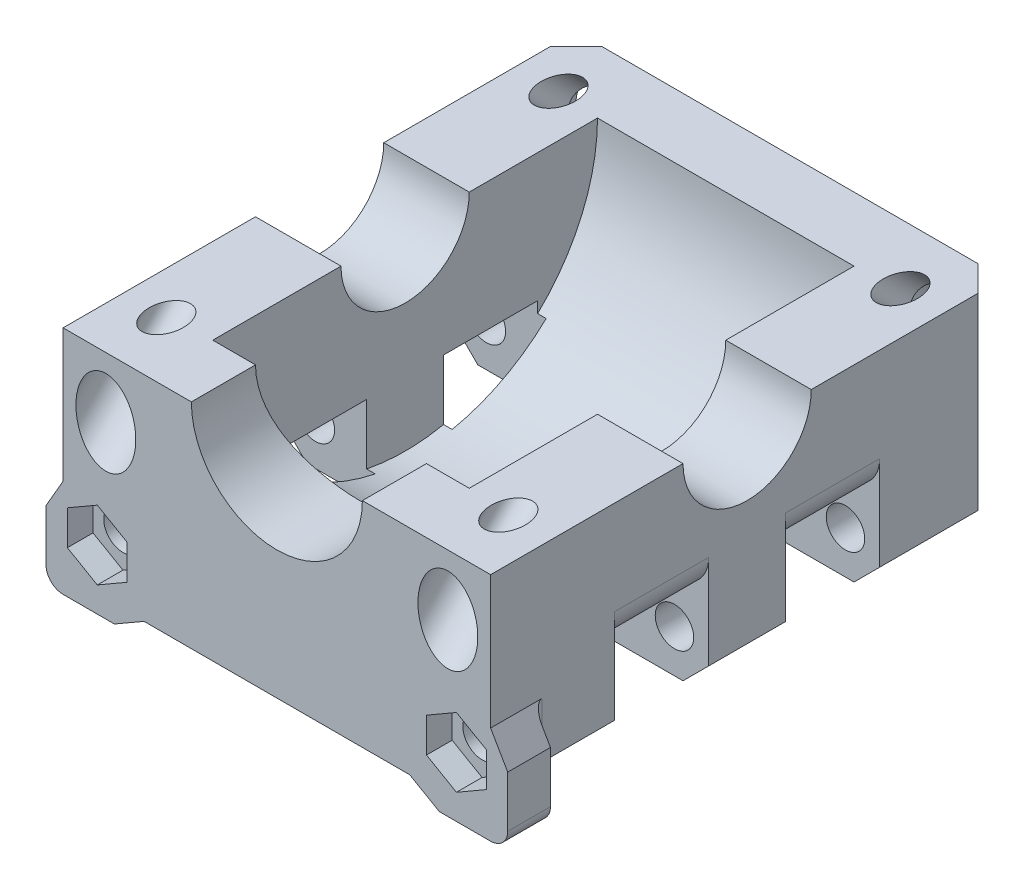
SolidWorks part; units mm, degrees
ref_plane "Front Plane" through (0, 0, 0) normal (0, 0, 1) x (1, 0, 0)
ref_plane "Top Plane" through (0, 0, 0) normal (0, 1, 0) x (1, 0, 0)
ref_plane "Right Plane" through (0, 0, 0) normal (1, 0, 0) x (0, 0, -1)
sketch "Sketch1" plane through (0, 0, 0) normal (0, 1, 0) x (1, 0, 0)
  line L1 (-25, 30) -> (25, 30)
  line L2 (-25, 30) -> (-25, -30)
  line L3 (-25, -30) -> (25, -30)
  line L4 (25, 30) -> (25, -30)
  line L5 (-25, 30) -> (25, -30) construction
  line L6 (-25, -30) -> (25, 30) construction
  point P0 (0, 0)
  dimension "D1" = 50
  dimension "D2" = 60
extrude "Boss-Extrude1" add sketch "Sketch1" along normal blind 25
sketch "Sketch2" plane through (-25, 0, 0) normal (-1, 0, 0) x (0, 0, 1)
  line L3 (-30, 25) -> (30, 25) construction
  line L6 (-30, 25) -> (-30, 0) construction
  circle A1 centre (0, 25) radius 22.5
  dimension "D1" = 45
  dimension "D2" = 7.5
extrude "Cut-Extrude1" cut sketch "Sketch2" against normal blind 30 from offset 10 offset against normal yes
sketch "Sketch3" plane through (-25, 0, 0) normal (-1, 0, 0) x (0, 0, 1)
  line L0 (-30, 25) -> (30, 25) construction
  circle A0 centre (0, 25) radius 7.5
  dimension "D1" = 15
extrude "Cut-Extrude2" cut sketch "Sketch3" against normal through all
sketch "Sketch4" plane through (0, 0, 30) normal (0, 0, 1) x (1, 0, 0)
  line L0 (-25, 25) -> (25, 25) construction
  circle A0 centre (0, 25) radius 10
  dimension "D1" = 20
extrude "Cut-Extrude3" cut sketch "Sketch4" against normal blind 10
sketch "Sketch10" plane through (25, 0, 0) normal (1, 0, 0) x (0, 0, -1)
  line L0 (-30, 0) -> (30, 0) construction
  line L1 (-4.5, 0) -> (-15.5, 0)
  line L2 (-4.5, 0) -> (-4.5, 10)
  line L3 (-4.5, 10) -> (-15.5, 10)
  line L4 (-15.5, 0) -> (-15.5, 10)
  line L5 (-30, 25) -> (-30, 0) construction
  line L6 (4.5, 0) -> (15.5, 0)
  line L7 (4.5, 0) -> (4.5, 10)
  line L8 (4.5, 10) -> (15.5, 10)
  line L9 (15.5, 0) -> (15.5, 10)
  arc A1 (-7.5, 25) -> (7.5, 25) centre (0, 25) ccw construction
  dimension "D1" = 10
  dimension "D2" = 10
  dimension "D3" = 9
  dimension "D4" = 11
  dimension "D5" = 11
  dimension "D6" = 14.5
  dimension "D7" = 4.5
  dimension "D8" = 4.5
extrude "Cut-Extrude9" cut sketch "Sketch10" against normal blind 11
sketch "Sketch11" plane through (0, 0, -4.5) normal (0, 0, -1) x (-1, 0, 0)
  line L0 (-25, 10) -> (-25, 0) construction
  line L1 (-14, 0) -> (-25, 0) construction
  circle A0 centre (-21, 5) radius 2.25
  dimension "D3" = 4.5
  dimension "D1" = 4
  dimension "D2" = 5
extrude "Cut-Extrude10" cut sketch "Sketch11" against normal through all both and the other way through all
mirror "Mirror1" about plane through (0, 0, 0) normal (1, 0, 0) of "Cut-Extrude9", "Cut-Extrude10"
ref_plane "Plane1" through (0, -2.5, 2.5) normal (0, -0.7071, 0.7071) x (1, 0, 0)
sketch "Sketch12" plane through (0, -2.5, 2.5) normal (0, -0.7071, 0.7071) x (1, 0, 0)
  line L0 (-25, 38.8909) -> (-25, 21.2132) construction
  line L2 (-25, 38.8909) -> (-10, 38.8909) construction
  line L3 (10, 38.8909) -> (25, 38.8909) construction
  circle A0 centre (20, 33.8909) radius 2
  circle A1 centre (-20, 33.8909) radius 2
  dimension "D1" = 4
  dimension "D2" = 4
  dimension "D3" = 40
  dimension "D4" = 5
  dimension "D5" = 5
  dimension "D6" = 5
extrude "Cut-Extrude11" cut sketch "Sketch12" against normal through all both and the other way through all
sketch "Sketch13" plane through (0, -2.5, 2.5) normal (0, -0.7071, 0.7071) x (1, 0, 0)
  circle A0 centre (-20, 33.8909) radius 3.5
  circle A1 centre (20, 33.8909) radius 3.5
  dimension "D1" = 7
  dimension "D2" = 7
extrude "Cut-Extrude12" cut sketch "Sketch13" along normal through all
mirror "Mirror3" about plane through (0, 0, 0) normal (0, 0, 1) of "Cut-Extrude12", "Cut-Extrude11"
chamfer "Chamfer1" distance 3 angle 45 2 edges at (25, 12.5, -30) (-25, 12.5, -30)
fillet "Fillet1" radius 4 4 edges at (25, 10, 10) (25, 10, -10) (-25, 10, -10) (-25, 10, 10)
sketch "Sketch14" plane through (0, 0, 0) normal (0, -1, 0) x (1, 0, 0)
  circle A0 centre (-15, -20.2057) radius 2
  circle A1 centre (15, -20.2057) radius 2
  dimension "D1" = 4
  dimension "D2" = 4
  dimension "D3" = 30
  dimension "D4" = 15
extrude "Cut-Extrude13" cut sketch "Sketch14" against normal blind 10
sketch "Sketch15" plane through (0, 0, 30) normal (0, 0, 1) x (1, 0, 0)
  line L1 (-21, 0.9585) -> (-17.5, 2.9793)
  line L2 (-17.5, 2.9793) -> (-17.5, 7.0207)
  line L3 (-17.5, 7.0207) -> (-21, 9.0415)
  line L4 (-21, 9.0415) -> (-24.5, 7.0207)
  line L5 (-24.5, 7.0207) -> (-24.5, 2.9793)
  line L6 (-24.5, 2.9793) -> (-21, 0.9585)
  line L7 (21, 0.9585) -> (24.5, 2.9793)
  line L8 (24.5, 2.9793) -> (24.5, 7.0207)
  line L9 (24.5, 7.0207) -> (21, 9.0415)
  line L10 (21, 9.0415) -> (17.5, 7.0207)
  line L11 (17.5, 7.0207) -> (17.5, 2.9793)
  line L12 (17.5, 2.9793) -> (21, 0.9585)
  circle A0 centre (-21, 5) radius 3.5 construction
  circle A1 centre (21, 5) radius 3.5 construction
  dimension "D1" = 7
  dimension "D2" = 7
extrude "Cut-Extrude14" cut sketch "Sketch15" against normal blind 3
sketch "Sketch16" plane through (0, 0, 30) normal (0, 0, 1) x (1, 0, 0)
  line L0 (-25, 9.4641) -> (-27, 6)
  line L1 (-25, 25) -> (-25, 0) construction
  line L2 (-27, 6) -> (-27, 0)
  line L3 (-25, -2) -> (-19, -2)
  line L4 (-19, -2) -> (-15.5359, 0)
  line L5 (-15.5359, 0) -> (-25, 0)
  line L6 (-25, 0) -> (25, 0) construction
  line L7 (-25, 0) -> (-25, 9.4641)
  arc A0 (-27, 0) -> (-25, -2) centre (-25, 0) ccw
  point P11 (-27, -2)
  dimension "D7" = 2
  dimension "D1" = 8
  dimension "D2" = 8
  dimension "D3" = 4
  dimension "D4" = 2
  dimension "D5" = 2
  dimension "D6" = 4
extrude "Boss-Extrude2" add sketch "Sketch16" against normal blind 5
mirror "Mirror4" about plane through (0, 0, 0) normal (1, 0, 0) of "Boss-Extrude2"
chamfer "Chamfer2" distance 3 angle 45 9 edges at (-25, 0, 20.25) (-25, 0, 0) (-25, 0, -21.25) (-23.5, 0, -28.5) (0, 0, -30) (23.5, 0, -28.5) (25, 0, -21.25) (25, 0, 20.25) (25, 0, 0)
fillet "Fillet2" radius 1 6 edges at (23.5, 1.5, 25) (25, 6.2321, 25) (18.7679, 0, 25) (-25, 6.2321, 25) (-18.7679, 0, 25) (-23.5, 1.5, 25)
